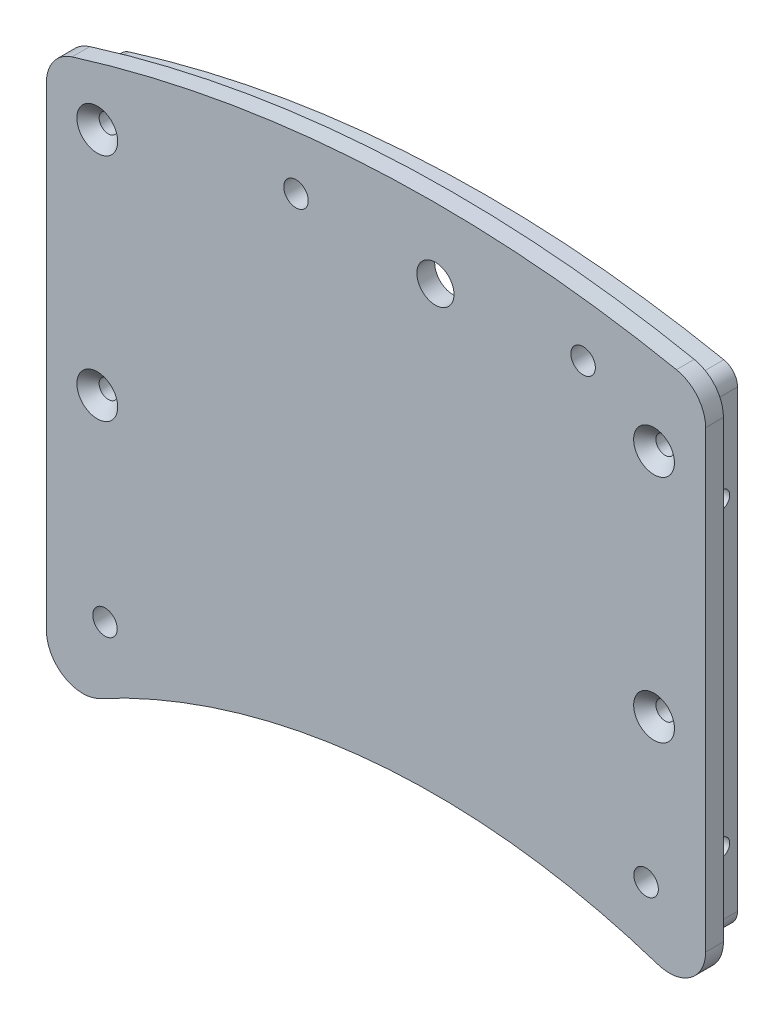
SolidWorks part; units mm, degrees
material "ABS"
ref_plane "Спереди" through (0, 0, 0) normal (0, 0, 1) x (1, 0, 0)
ref_plane "Сверху" through (0, 0, 0) normal (0, 1, 0) x (1, 0, 0)
ref_plane "Справа" through (0, 0, 0) normal (1, 0, 0) x (0, 0, -1)
sketch "Эскиз1" plane through (0, 0, 0) normal (0, 0, 1) x (1, 0, 0)
  line L4 (33.8, 95.2246) -> (33.8, 156.409)
  line L5 (-49.8, 152.3147) -> (-49.8, 88.3387)
  line L6 (33.8, 95.2246) -> (33.8, 156.409)
  line L7 (-49.8, 152.3147) -> (-49.8, 88.3387)
  arc A12 (33.8, 156.409) -> (31.9541, 158.6637) centre (31.5, 156.409) ccw
  arc A13 (30.7777, 93.041) -> (33.8, 95.2246) centre (31.5, 95.2246) ccw
  arc A14 (30.7777, 93.041) -> (-46.4108, 86.313) centre (0, 0) ccw
  arc A15 (-49.8, 88.3387) -> (-46.4108, 86.313) centre (-47.5, 88.3387) ccw
  arc A16 (-48.1847, 154.5104) -> (-49.8, 152.3147) centre (-47.5, 152.3147) ccw
  arc A17 (31.9541, 158.6637) -> (-48.1847, 154.5104) centre (0, 0) ccw
  arc A18 (33.8, 156.409) -> (31.9541, 158.6637) centre (31.5, 156.409) ccw
  arc A19 (30.7777, 93.041) -> (33.8, 95.2246) centre (31.5, 95.2246) ccw
  arc A20 (30.7777, 93.041) -> (-46.4108, 86.313) centre (0, 0) ccw
  arc A21 (-49.8, 88.3387) -> (-46.4108, 86.313) centre (-47.5, 88.3387) ccw
  arc A22 (-48.1847, 154.5104) -> (-49.8, 152.3147) centre (-47.5, 152.3147) ccw
  arc A23 (31.9541, 158.6637) -> (-48.1847, 154.5104) centre (0, 0) ccw
  dimension "D1" = 0.2
extrude "Внутренний бортик" add sketch "Эскиз1" against normal blind 4.5 thin thin type one direction reverse wall 2.4
sketch "Эскиз2" plane through (0, 0, 0) normal (0, 0, 1) x (1, 0, 0)
  line L1 (36.4, 156.409) -> (36.4, 95.2246) construction
  line L2 (-52.4, 152.3147) -> (-52.4, 88.3387)
  line L3 (36.4, 156.409) -> (36.4, 95.2246)
  arc A0 (-48.9588, 156.9925) -> (-52.4, 152.3147) centre (-47.5, 152.3147) ccw construction
  arc A1 (-52.4, 88.3387) -> (-45.1794, 84.023) centre (-47.5, 88.3387) ccw construction
  arc A2 (29.9611, 90.5725) -> (-45.1794, 84.023) centre (0, 0) ccw construction
  arc A3 (29.9611, 90.5725) -> (36.4, 95.2246) centre (31.5, 95.2246) ccw construction
  arc A4 (36.4, 156.409) -> (32.4674, 161.2125) centre (31.5, 156.409) ccw construction
  arc A5 (32.4674, 161.2125) -> (-48.9588, 156.9925) centre (0, 0) ccw construction
  arc A6 (-48.9588, 156.9925) -> (-52.4, 152.3147) centre (-47.5, 152.3147) ccw
  arc A7 (-52.4, 88.3387) -> (-45.1794, 84.023) centre (-47.5, 88.3387) ccw
  arc A8 (29.9611, 90.5725) -> (-45.1794, 84.023) centre (0, 0) ccw
  arc A9 (29.9611, 90.5725) -> (36.4, 95.2246) centre (31.5, 95.2246) ccw
  arc A10 (36.4, 156.409) -> (32.4674, 161.2125) centre (31.5, 156.409) ccw
  arc A11 (32.4674, 161.2125) -> (-48.9588, 156.9925) centre (0, 0) ccw
extrude "Крышка" add sketch "Эскиз2" along normal blind 2.4
sketch "Эскиз7" plane through (0, 0, 0) normal (0, 0, -1) x (-1, 0, 0)
  circle A0 centre (-29.4514, 150.2003) radius 1.25
  circle A1 centre (45.5549, 150.2004) radius 1.25
  circle A2 centre (45.5509, 119.2092) radius 1.25
  circle A3 centre (-29.4544, 119.2087) radius 1.25
  circle A7 centre (0, 155) radius 2.5
  dimension "D1" = 2.5
extrude "Крпежные отверстия платы" cut sketch "Эскиз7" against normal blind 3
chamfer "Фаска крепежных отверстий платы" distance 1.5 angle 45 4 edges at (-44.3009, 119.2092, 2.4) (30.7044, 119.2087, 2.4) (30.7014, 150.2003, 2.4) (-44.3049, 150.2004, 2.4)
sketch "Эскиз8" plane through (0, 0, 0) normal (0, 0, -1) x (-1, 0, 0)
  circle A0 centre (-29.4544, 119.2087) radius 1.25 construction
  circle A1 centre (-29.4514, 150.2003) radius 1.25 construction
  circle A2 centre (45.5509, 119.2092) radius 1.25 construction
  circle A3 centre (45.5549, 150.2004) radius 1.25 construction
  circle A4 centre (-29.4544, 119.2087) radius 1.25
  circle A5 centre (-29.4514, 150.2003) radius 1.25
  circle A6 centre (45.5509, 119.2092) radius 1.25
  circle A7 centre (45.5549, 150.2004) radius 1.25
  circle A8 centre (-29.4544, 119.2087) radius 2.85
  circle A9 centre (-29.4514, 150.2003) radius 2.85
  circle A10 centre (45.5509, 119.2092) radius 2.85
  circle A11 centre (45.5549, 150.2004) radius 2.85
  dimension "D1" = 1.6
extrude "Стойки для платы" add sketch "Эскиз8" along normal blind 4.5
sketch "Эскиз9" plane through (0, 0, 0) normal (0, 0, -1) x (-1, 0, 0)
  line L0 (-28.3808, 99.3817) -> (0, 0) construction
  line L1 (0, 0) -> (44.5125, 93.2783) construction
  line L2 (-19.8949, 155.97) -> (0, 0) construction
  line L3 (0, 0) -> (18.7834, 156.1077) construction
  circle A0 centre (-28.3808, 99.3817) radius 1.65
  circle A1 centre (44.5125, 93.2783) radius 1.65
  circle A2 centre (-19.8949, 155.97) radius 1.65
  circle A3 centre (18.7834, 156.1077) radius 1.65
  dimension "D1" = 3.3
extrude "Отверстия крепления к телескопу" cut sketch "Эскиз9" against normal blind 3
sketch "Эскиз13" plane through (-49.8, 0, 0) normal (-1, 0, 0) x (0, 0, 1)
  circle A0 centre (-2.25, 144.3147) radius 1.2
  circle A1 centre (-2.25, 91.4387) radius 1.2
  circle A2 centre (-2.25, 91.4387) radius 1.4 construction
  circle A3 centre (-2.25, 144.3147) radius 1.4 construction
  dimension "D1" = 2.4
  dimension "D2" = 2.4
extrude "Крепежные отверстия правые" cut sketch "Эскиз13" against normal blind 5
sketch "Эскиз14" plane through (33.8, 0, 0) normal (1, 0, 0) x (0, 0, -1)
  circle A0 centre (2.25, 144.3147) radius 1.2
  circle A1 centre (2.25, 103.7246) radius 1.2
  circle A2 centre (2.25, 103.7246) radius 1.4 construction
  circle A3 centre (2.25, 144.3147) radius 1.4 construction
  circle A4 centre (2.25, 144.3147) radius 1.2 construction
extrude "Крепежные отверстия левые" cut sketch "Эскиз14" against normal blind 7
fillet "Скругление внутреннего бортика" radius 2 4 edges at (31.4, 156.3271, -2.25) (-44.944, 152.9841, -2.25) (31.4, 95.3629, -2.25) (-47.4, 88.5058, -2.25)
